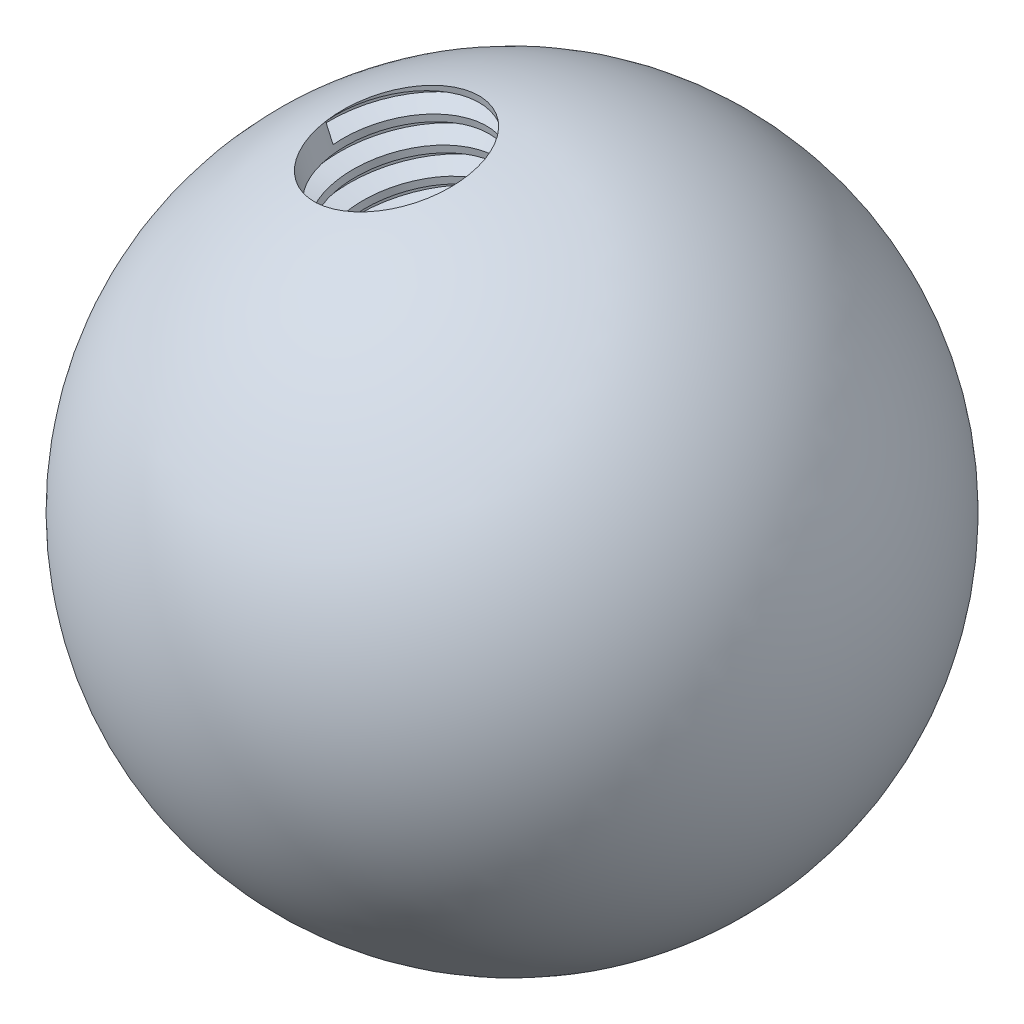
SolidWorks part; units mm, degrees
material "AISI 316L"
ref_plane "Piano frontale" through (0, 0, 0) normal (0, 0, 1) x (1, 0, 0)
ref_plane "Piano superiore" through (0, 0, 0) normal (0, 1, 0) x (1, 0, 0)
ref_plane "Piano destro" through (0, 0, 0) normal (1, 0, 0) x (0, 0, -1)
sketch "Schizzo1" plane through (0, 0, 0) normal (0, 0, 1) x (1, 0, 0)
  line L0 (0.6636, 14.9853) -> (-0.6636, -14.9853)
  arc A0 (0.6636, 14.9853) -> (-0.6636, -14.9853) centre (0, 0) ccw
  dimension "D1" = 30
revolve "Rivoluzione1" add sketch "Schizzo1" angle 360 about L0
hole_wizard "Preforo da maschiare M8x1.25-1" positions "Schizzo3D1" profile "Schizzo2" hole size "M8x1.25" standard "Ansi Metric"
sketch3d "Schizzo3D1"
  point P0 (0, 0, 0)
  point P3 (0, 0, 0)
  point P5 (-2.9015, 14.5029, 2.4995)
sketch "Schizzo2" plane through (-2.9015, 14.5029, 2.4995) normal (0.707, 0.0196, 0.707) x (-0.6803, -0.2546, 0.6873)
  line L0 (0, 0) -> (0, 15)
  line L1 (0, 15) -> (3.4, 12.9571)
  line L2 (3.4, 12.9571) -> (3.4, 0)
  line L5 (3.4, 0) -> (0, 0)
  line L10 (0, 15) -> (-3.4, 12.9571) construction
  line L11 (0, -6.35) -> (0, 107.95) construction
  dimension "Hole Dia." = 6.8
  dimension "Hole Depth" = 15
  dimension "Drill Angle" = 118
thread "Filettatura1" pitch 1.25 method cut profile "Profilo filettatura1" start angle 0, offset 0, length 15, pitch 1.25, diameter 6.8
ref_plane "Piano1" through (-6.1618, 13.4773, 2.3228) normal (0, -0.1698, 0.9855) x (-0.9811, -0.1906, -0.0329)
sketch "Profilo filettatura1" plane through (-6.1618, 13.4773, 2.3228) normal (0, -0.1698, 0.9855) x (-0.9811, -0.1906, -0.0329)
  line L0 (0, 0) -> (0, 1.25) construction
  line L1 (0, 0) -> (0.6766, 0.3906)
  line L2 (0.6766, 0.3906) -> (0.6766, 0.5469)
  line L3 (0.6766, 0.5469) -> (0, 0.9375)
  line L4 (0.6766, 0.4687) -> (0, 0.4687) construction
  line L11 (0, 0) -> (0, 0.9375)
  point P2 (0, 0)
  dimension "Pitch" = 1.25
  dimension "Profile_Angle" = 60
  dimension "Profile_Land" = 0.1562
  dimension "Profile_Height" = 0.6766
